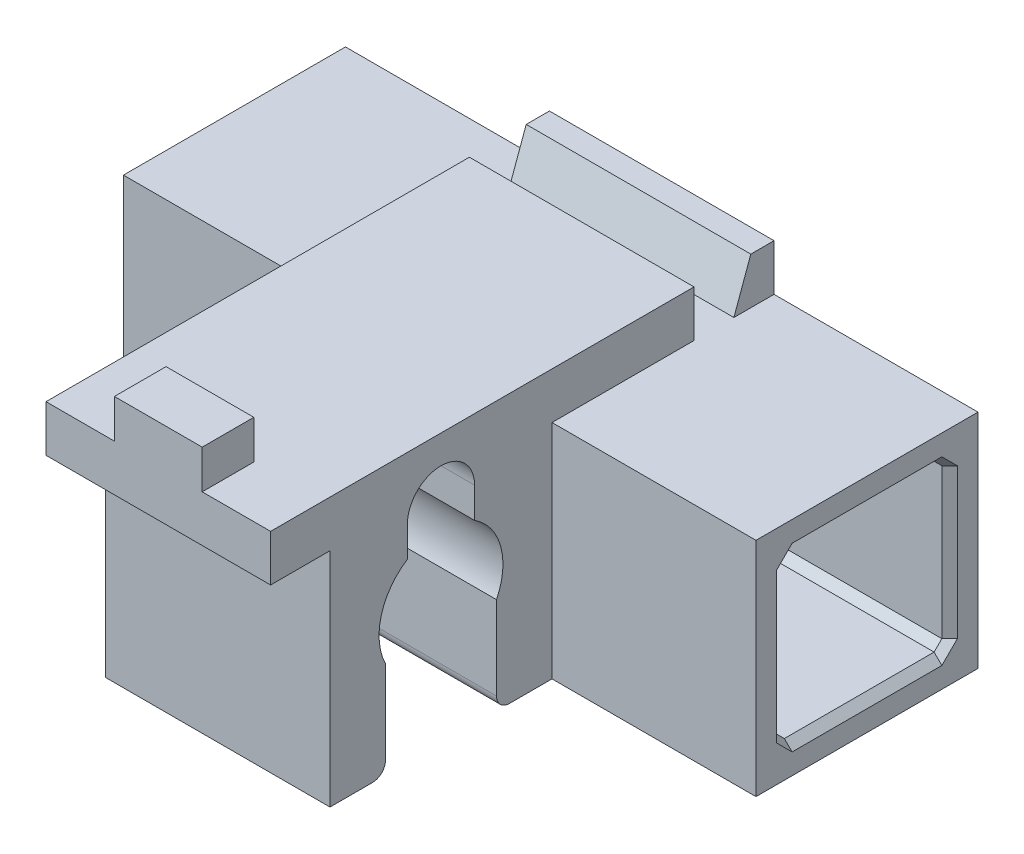
SolidWorks part; units mm, degrees
ref_plane "Front Plane" through (0, 0, 0) normal (0, 0, 1) x (1, 0, 0)
ref_plane "Top Plane" through (0, 0, 0) normal (0, 1, 0) x (1, 0, 0)
ref_plane "Right Plane" through (0, 0, 0) normal (1, 0, 0) x (0, 0, -1)
sketch "Sketch2" plane through (0, 0, 0) normal (1, 0, 0) x (0, 0, -1)
  line L1 (-4.3, -4.3) -> (4.3, -4.3)
  line L2 (-4.3, -4.3) -> (-4.3, 4.3)
  line L3 (-4.3, 4.3) -> (4.3, 4.3)
  line L4 (4.3, -4.3) -> (4.3, 4.3)
  line L5 (-4.3, -4.3) -> (4.3, 4.3) construction
  line L6 (-4.3, 4.3) -> (4.3, -4.3) construction
  point P0 (0, 0)
  dimension "D1" = 8.6
  dimension "D2" = 8.6
extrude "Extrude-Thin1" add sketch "Sketch2" along normal mid plane 24.5 thin thin type one direction reverse wall 1.1
chamfer "Chamfer1" distance 0.3 angle 45 12 edges at (0, -3.2, -3.2) (12.25, -3.2, 0) (0, -3.2, 3.2) (-12.25, -3.2, 0) (12.25, 0, 3.2) (-12.25, 0, 3.2) (12.25, 0, -3.2) (-12.25, 0, -3.2) (0, 3.2, 3.2) (12.25, 3.2, 0) (0, 3.2, -3.2) (-12.25, 3.2, 0)
sketch "Sketch3" plane through (12.25, 0, 0) normal (1, 0, 0) x (0, 0, -1)
  line L0 (2.9, 3.2) -> (-2.9, 3.2) construction
  line L1 (-2.1913, 3.2) -> (-1.5913, 3.2)
  line L2 (-2.1913, 3.2) -> (-2.1913, -3.2)
  line L3 (-2.1913, -3.2) -> (-1.5913, -3.2)
  line L4 (-1.5913, 3.2) -> (-1.5913, -3.2)
  line L5 (-2.9, -3.2) -> (2.9, -3.2) construction
  line L7 (3.2, -2.9) -> (3.2, 2.9) construction
  line L8 (-1.5913, -1) -> (-2.1913, -1)
  line L9 (-1.5913, 1) -> (-2.1913, 1)
  line L10 (0, 0) -> (0.7, 0) construction
  circle A0 centre (0.7, 0) radius 2.5 construction
  dimension "D2" = 5
  dimension "D1" = 0.6
  dimension "D3" = 2
extrude "Boss-Extrude1" add sketch "Sketch3" along normal mid plane 10 from surface contours L9 L4 L1 L2 | L4 L8 L2 L3 region at (12.25, 2.1, 1.8913) region at (12.25, -2.1, 1.8913) starting at plane "Right Plane"
sketch "Sketch4" plane through (0, 0, -4.3) normal (0, 0, -1) x (-1, 0, 0)
  line L0 (-12.25, 4.3) -> (12.25, 4.3) construction
  line L1 (-4.35, 4.3) -> (4.35, 4.3)
  line L2 (-4.35, 4.3) -> (-4.35, 6.1)
  line L3 (-4.35, 6.1) -> (4.35, 6.1)
  line L4 (4.35, 4.3) -> (4.35, 6.1)
  line L5 (0, 6.1) -> (0, 0) construction
  dimension "D1" = 8.7
  dimension "D2" = 1.8
extrude "Boss-Extrude2" add sketch "Sketch4" against normal blind 19.5
sketch "Sketch5" plane through (4.35, 0, 0) normal (1, 0, 0) x (0, 0, -1)
  line L0 (-15.2, 6.1) -> (4.3, 6.1) construction
  line L1 (2.7, 6.1) -> (1.2, 6.1)
  line L2 (2.7, 6.1) -> (2.7, 4.3)
  line L3 (2.7, 4.3) -> (1.2, 4.3)
  line L4 (1.2, 6.1) -> (1.2, 4.3)
  line L5 (-4.3, 4.3) -> (4.3, 4.3) construction
  line L6 (4.3, 6.1) -> (4.3, 4.3) construction
  dimension "D1" = 1.5
  dimension "D2" = 1.6
extrude "Cut-Extrude1" cut sketch "Sketch5" against normal up to next
chamfer "Chamfer2" distance 0.7 angle 70 1 edges at (0, 6.1, -2.7) first distance on face at (0, 6.1, -3.5)
sketch "Sketch6" plane through (0, 0, 15.2) normal (0, 0, 1) x (1, 0, 0)
  line L0 (-4.35, 6.1) -> (4.35, 6.1) construction
  line L1 (-1.7, 6.1) -> (1.7, 6.1)
  line L2 (-1.7, 6.1) -> (-1.7, 7.6)
  line L3 (-1.7, 7.6) -> (1.7, 7.6)
  line L4 (1.7, 6.1) -> (1.7, 7.6)
  line L5 (0, 7.6) -> (0, 0) construction
  dimension "D1" = 3.4
  dimension "D2" = 1.5
extrude "Boss-Extrude3" add sketch "Sketch6" against normal blind 2
sketch "Sketch7" plane through (4.35, 0, 0) normal (1, 0, 0) x (0, 0, -1)
  line L0 (-8.6, 0.5) -> (-8.6, 3.7) construction
  line L1 (-4.3, 4.3) -> (-12.9, 4.3)
  line L2 (-4.3, 4.3) -> (-4.3, -4.3)
  line L3 (-4.3, -4.3) -> (-12.9, -4.3)
  line L4 (-12.9, 4.3) -> (-12.9, -4.3)
  line L5 (-9.9, 0.5) -> (-9.9, 3.7)
  line L6 (-7.3, 0.5) -> (-7.3, 3.7)
  line L7 (-4.3, -4.3) -> (4.3, -4.3) construction
  line L8 (-8.6, 0.5) -> (-8.6, -4.3) construction
  line L10 (-10.75, -0.5665) -> (-6.45, -0.5665)
  line L11 (-10.75, -0.5665) -> (-10.75, -4.3)
  line L12 (-10.75, -4.3) -> (-6.45, -4.3)
  line L13 (-6.45, -0.5665) -> (-6.45, -4.3)
  circle A0 centre (-8.6, 0.5) radius 2.4
  arc A1 (-9.9, 0.5) -> (-7.3, 0.5) centre (-8.6, 0.5) ccw
  arc A2 (-7.3, 3.7) -> (-9.9, 3.7) centre (-8.6, 3.7) ccw
  point P7 (-8.6, 2.1)
  point P21 (-8.6, -0.5665)
  line M19 (-15.2, 4.3) -> (-4.3, 4.3)
  dimension "D1" = 4.8
  dimension "D2" = 2.6
  dimension "D3" = 8
  dimension "D4" = 8.6
  dimension "D5" = 4.8
  dimension "D6" = 4.3
extrude "Boss-Extrude4" add sketch "Sketch7" against normal up to surface (8.7 mm away) contours A2 L4 L3 L11 A0 L5 M19 | A2 L6 A0 L13 L3 L2 M19 region at (4.35, 0.292, 5.4959) region at (4.35, 0.292, 11.7041) up to face at (-4.35, 5.02, 6.46)
extrude "Cut-Extrude2" cut sketch "Sketch7<3>" against normal up to next contours L1 A2 region at (4.35, 4.5877, 8.6)
sketch "Sketch7<3>" plane through (4.35, 0, 0) normal (1, 0, 0) x (0, 0, -1) same geometry as "Sketch7"
fillet "Fillet1" radius 0.5 2 edges at (0, -4.3, 6.45) (0, -4.3, 10.75)
sketch "Sketch8" plane through (0, 0, -4.3) normal (0, 0, -1) x (-1, 0, 0)
  line L0 (-8.2, -1.1) -> (-8.2, 3.3)
  line L9 (-8.2, 3.3) -> (-4.2, 3.3)
  line L10 (-4.2, -1.1) -> (-4.2, 3.3)
  line L11 (-7.5, -0.4) -> (-4.9, -0.4)
  line L12 (-7.5, -0.4) -> (-7.5, 2.6)
  line L13 (-7.5, 2.6) -> (-4.9, 2.6)
  line L14 (-4.9, -0.4) -> (-4.9, 2.6)
  line L15 (-7.5, -0.4) -> (-4.9, 2.6) construction
  line L16 (-7.5, 2.6) -> (-4.9, -0.4) construction
  line L17 (-8.2, -1.1) -> (-4.2, -1.1)
  line L18 (0, -4.3) -> (0, 6.1) construction
  line L19 (-12.25, -4.3) -> (12.25, -4.3) construction
  line L20 (4.35, 6.1) -> (-4.35, 6.1) construction
  line L21 (7.5, 2.6) -> (4.9, -0.4) construction
  line L22 (7.5, -0.4) -> (4.9, 2.6) construction
  line L23 (8.2, -1.1) -> (4.2, -1.1)
  line L24 (4.9, -0.4) -> (4.9, 2.6)
  line L25 (7.5, 2.6) -> (4.9, 2.6)
  line L26 (7.5, -0.4) -> (7.5, 2.6)
  line L27 (7.5, -0.4) -> (4.9, -0.4)
  line L28 (4.2, -1.1) -> (4.2, 3.3)
  line L29 (8.2, 3.3) -> (4.2, 3.3)
  line L30 (8.2, -1.1) -> (8.2, 3.3)
  line L31 (-6.2, 1.1) -> (-4.2, 1.1) construction
  line L40 (-4.2, 1.8) -> (4.2, 1.8)
  line L41 (-4.2, 1.8) -> (-4.2, 0.4)
  line L42 (-4.2, 0.4) -> (4.2, 0.4)
  line L43 (4.2, 1.8) -> (4.2, 0.4)
  line L44 (-4.2, 2.3) -> (4.2, 2.3)
  line L45 (-4.2, 2.3) -> (-4.2, -0.1)
  line L46 (-4.2, -0.1) -> (4.2, -0.1)
  line L47 (4.2, 2.3) -> (4.2, -0.1)
  point P0 (-6.2, 1.1)
  point P5 (-6.2, 1.1)
  point P20 (6.2, 1.1)
  point P33 (-4.2, 1.1)
  point P34 (-4.2, 1.1)
  dimension "D1" = 3
  dimension "D2" = 2.6
  dimension "D4" = 1.4
  dimension "D5" = 2.4
  dimension "D6" = 16.4
  dimension "D7" = 6.1
  dimension "D3" = 0.7
extrude "Cut-Extrude3" cut sketch "Sketch8" against normal blind 0.3 contours L0 L17 L10 L9 L14 L11 L12 L13 | L44 L10 L40 L28 | L10 L46 L28 L42 | L23 L30 L29 L28 L26 L27 L24 L25 region at (8.1405, 1.1, -4.3) region at (0, 0.15, -4.3) region at (0, 2.05, -4.3) region at (-4.2595, 0.15, -4.3)
